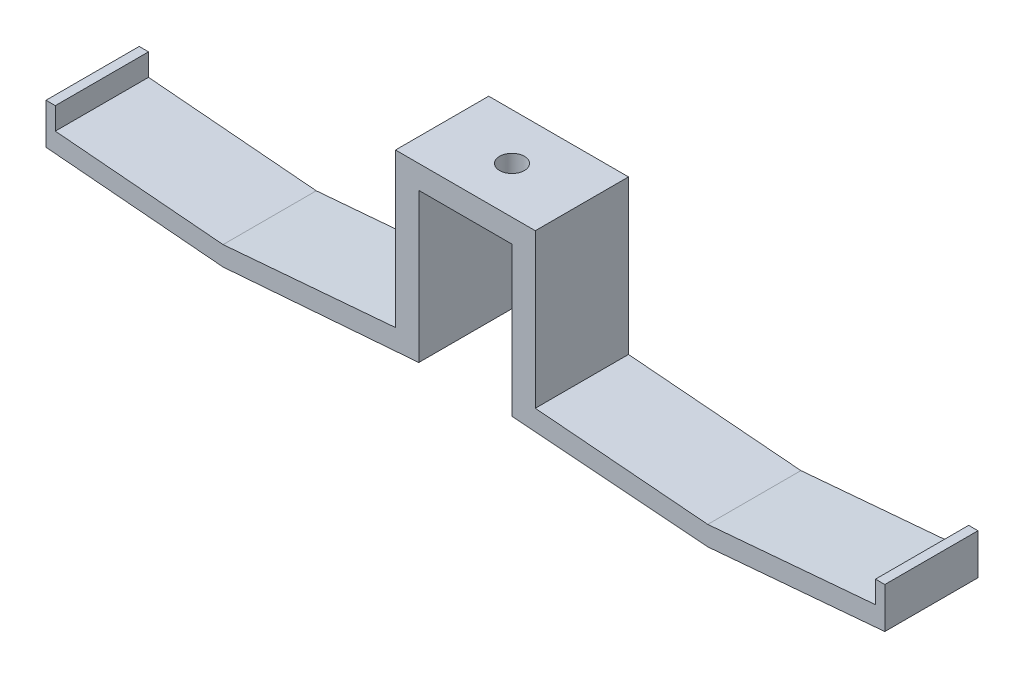
SolidWorks part; units mm, degrees
material "Nylon 6/10"
ref_plane "Front Plane" through (0, 0, 0) normal (0, 0, 1) x (1, 0, 0)
ref_plane "Top Plane" through (0, 0, 0) normal (0, 1, 0) x (1, 0, 0)
ref_plane "Right Plane" through (0, 0, 0) normal (1, 0, 0) x (0, 0, -1)
other "Center of Mass"
sketch "Sketch2" plane through (0, 0, 0) normal (0, 0, 1) x (1, 0, 0)
  line L1 (12.7, 0) -> (12.7, -40.64)
  line L2 (12.7, -40.64) -> (66.04, -44.7734)
  line L3 (66.04, -44.7734) -> (114.3, -40.64)
  line L4 (114.3, -40.64) -> (114.3, -29.5334)
  line L5 (111.76, -29.5334) -> (111.76, -35.56)
  line L6 (111.76, -35.56) -> (66.04, -39.4758)
  line L19 (114.3, -29.5334) -> (111.76, -29.5334)
  line L20 (0, 125.2351) -> (0, -75.9356) construction
  line L21 (12.7, 0) -> (-12.7, 0)
  line L22 (0, 0) -> (0, 6.35)
  line L23 (19.05, 6.35) -> (-19.05, 6.35)
  line L24 (19.05, 6.35) -> (19.05, 0)
  line L25 (19.05, 0) -> (19.05, -35.56)
  line L26 (19.05, -35.56) -> (66.04, -39.4758)
  line L27 (-19.05, 0) -> (-19.05, -35.56)
  line L28 (-19.05, 6.35) -> (-19.05, 0)
  line L29 (-12.7, 0) -> (-12.7, -40.64)
  line L30 (-12.7, -40.64) -> (-66.04, -44.7734)
  line L31 (-66.04, -44.7734) -> (-114.3, -40.64)
  line L32 (-114.3, -40.64) -> (-114.3, -29.5334)
  line L33 (-114.3, -29.5334) -> (-111.76, -29.5334)
  line L34 (-111.76, -29.5334) -> (-111.76, -35.56)
  line L35 (-111.76, -35.56) -> (-66.04, -39.4758)
  line L36 (-19.05, -35.56) -> (-66.04, -39.4758)
  dimension "D1" = 19.05
  dimension "D2" = 12.7
  dimension "D3" = 35.56
  dimension "D4" = 3.9158
  dimension "D5" = 40.64
  dimension "D6" = 2.54
  dimension "D7" = 45.72
  dimension "D8" = 46.99
  dimension "D9" = 15.24
  dimension "D10" = 6.35
extrude "Boss-Extrude1" add sketch "Sketch2" along normal blind 25.4 contours L26 L25 L24 L23 L22 L21 L1 L2 L3 L4 L19 L5 L6 | L27 L36 L35 L34 L33 L32 L31 L30 L29 L21 L22 L23 L28 region at (6.35, 1.2521, 0) region at (-6.35, 1.2521, 0)
sketch "Sketch3" plane through (0, 6.35, 0) normal (0, 1, 0) x (1, 0, 0)
  line L0 (19.05, -12.7) -> (-19.05, -12.7) construction
  line L1 (19.05, -25.4) -> (19.05, 0) construction
  line L2 (-19.05, -25.4) -> (-19.05, 0) construction
  circle A0 centre (0, -12.7) radius 3.3782
  dimension "D1" = 6.7564
extrude "Cut-Extrude1" cut sketch "Sketch3" against normal up to next and the other way through all
